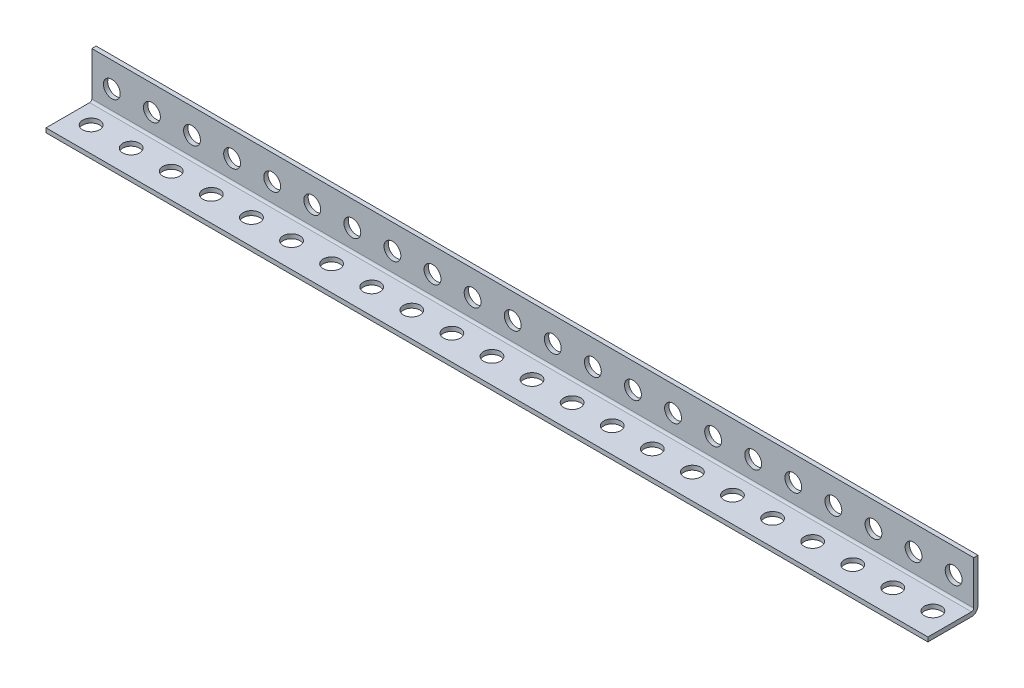
SolidWorks part; units mm, degrees
ref_plane "Front Plane" through (0, 0, 0) normal (0, 0, 1) x (1, 0, 0)
ref_plane "Top Plane" through (0, 0, 0) normal (0, 1, 0) x (1, 0, 0)
ref_plane "Right Plane" through (0, 0, 0) normal (1, 0, 0) x (0, 0, -1)
sketch "Sketch1" plane through (0, 0, 0) normal (1, 0, 0) x (0, 0, -1)
  line L0 (-15.875, -13.1318) -> (13.1318, -13.1318) construction
  line L1 (13.1318, -13.1318) -> (13.1318, 15.875) construction
  line L2 (13.1318, 15.875) -> (15.875, 15.875) construction
  line L3 (15.875, 15.875) -> (15.875, -15.875) construction
  line L4 (15.875, -15.875) -> (-15.875, -15.875) construction
  line L5 (-15.875, -15.875) -> (-15.875, -13.1318) construction
  line L6 (0, -15.875) -> (0, 15.875) construction
  line L7 (15.875, 0) -> (-15.875, 0) construction
  dimension "Thickness | T" = 2.7432
  dimension "Width (A)" = 31.75
  dimension "Width (B)" = 31.75
sketch "Sketch2" plane through (0, 0, 0) normal (0, 0, 1) x (1, 0, 0)
  line L0 (-609.6, 0) -> (609.6, 0) construction
  line L1 (-609.6, 15.875) -> (609.6, 15.875) construction
  line L2 (-609.6, 15.875) -> (-609.6, -15.875) construction
  line L3 (-609.6, -15.875) -> (609.6, -15.875) construction
  line L4 (609.6, 15.875) -> (609.6, -15.875) construction
  line L5 (0, 15.875) -> (0, -15.875) construction
  line L7 (-609.6, -13.1318) -> (609.6, -13.1318) construction
  circle A0 centre (596.9, 0) radius 5.334 construction
  circle A1 centre (571.5, 0) radius 5.334 construction
  point P15 (533.4, 0)
  point P16 (-533.4, 0)
  point P24 (602.234, 0)
  dimension "Mounting Hole Diameter" = 10.668
  dimension "Length | L" = 1219.2
  dimension "Mounting Hole Center to Center" = 25.4
  dimension "D1" = 12.7
  dimension "D2" = 63.5
sketch "Sketch3" plane through (0, 0, 0) normal (0, 1, 0) x (1, 0, 0)
  line L1 (-609.6, 15.875) -> (609.6, 15.875) construction
  line L2 (-609.6, 15.875) -> (-609.6, -15.875) construction
  line L3 (-609.6, -15.875) -> (609.6, -15.875) construction
  line L4 (609.6, 15.875) -> (609.6, -15.875) construction
  line L5 (-609.6, 13.1318) -> (609.6, 13.1318) construction
  line L7 (-609.6, 0) -> (609.6, 0) construction
  circle A0 centre (596.9, 0) radius 5.334 construction
  circle A1 centre (571.5, 0) radius 5.334 construction
  point P19 (-533.4, 0)
  point P21 (602.234, 0)
  point P22 (533.4, 0)
sketch "Sketch4" plane through (0, 0, 0) normal (1, 0, 0) x (0, 0, -1)
  line L0 (-15.875, -13.1318) -> (11.7602, -13.1318)
  line L1 (13.1318, -11.7602) -> (13.1318, 15.875)
  line L2 (13.1318, 15.875) -> (15.875, 15.875)
  line L3 (15.875, 15.875) -> (15.875, -11.7602)
  line L4 (11.7602, -15.875) -> (-15.875, -15.875)
  line L5 (-15.875, -15.875) -> (-15.875, -13.1318)
  line L6 (11.7602, -13.1318) -> (11.7602, -10.3886) construction
  arc A0 (11.7602, -13.1318) -> (13.1318, -11.7602) centre (11.7602, -11.7602) ccw
  arc A1 (15.875, -11.7602) -> (11.7602, -15.875) centre (11.7602, -11.7602) cw
extrude "Boss-Extrude1" add sketch "Sketch4" along normal up to vertex (609.6 mm away) and the other way up to vertex (609.6 mm away) up to point (609.6, 0, 0) other way up to point (-609.6, 0, 0)
sketch "Sketch5" plane through (0, 0, 0) normal (0, 0, 1) x (1, 0, 0)
  circle A0 centre (596.9, 0) radius 5.334
extrude "Cut-Extrude1" cut sketch "Sketch5" against normal through all
sketch "Sketch6" plane through (0, 0, 0) normal (0, 1, 0) x (1, 0, 0)
  circle A0 centre (596.9, 0) radius 5.334
extrude "Cut-Extrude2" cut sketch "Sketch6" against normal through all
pattern_linear "LPattern1" count 48 spacing 25.4 along (-1, 0, 0) of "Cut-Extrude2", "Cut-Extrude1"
sketch "Sketch7" plane through (0, 0, -15.875) normal (0, 0, -1) x (-1, 0, 0)
  line L0 (-609.6, -15.875) -> (609.6, -15.875) construction
  line L1 (-609.6, 15.875) -> (25.4, 15.875)
  line L2 (-609.6, 15.875) -> (-609.6, -15.875)
  line L3 (-609.6, -15.875) -> (25.4, -15.875)
  line L4 (25.4, 15.875) -> (25.4, -15.875)
  line L5 (602.234, 0) -> (609.6, 0) construction
  line L6 (609.6, -11.7602) -> (609.6, 15.875) construction
  line L7 (32.766, 0) -> (25.4, 0)
  circle A0 centre (596.9, 0) radius 5.334 construction
  circle A1 centre (38.1, 0) radius 5.334 construction
  dimension "D1" = 7.366
extrude "Cut-Extrude3" cut sketch "Sketch7" against normal blind 70 contours L4 L1 L2 L3 region at (292.1, 0, -15.875)
sketch "Sketch8" plane through (0, 0, -15.875) normal (0, 0, -1) x (-1, 0, 0)
  line L0 (25.4, -15.875) -> (609.6, -15.875) construction
  line L1 (25.4, 15.875) -> (50.8, 15.875)
  line L2 (25.4, 15.875) -> (25.4, -15.875)
  line L3 (25.4, -15.875) -> (50.8, -15.875)
  line L4 (50.8, 15.875) -> (50.8, -15.875)
  line L6 (58.166, 0) -> (50.8, 0)
  circle A0 centre (63.5, 0) radius 5.334 construction
  circle M28 centre (38.1, 0) radius 5.334
  line M29 (25.4, 15.875) -> (25.4, -11.7602)
  line M30 (25.4, -11.7602) -> (609.6, -11.7602)
  line M32 (609.6, 15.875) -> (25.4, 15.875)
  dimension "D1" = 7.366
extrude "Cut-Extrude4" cut sketch "Sketch8" against normal blind 70 contours L4 M32 M29 M30 M28 | L4 L2 L3 M30 region at (-38.1, 15.4997, -15.875) region at (-38.1, -13.8176, -15.875)
sketch "Sketch9" plane through (0, 0, -15.875) normal (0, 0, -1) x (-1, 0, 0)
  line L0 (602.234, 0) -> (609.6, 0)
  line L1 (609.6, -11.7602) -> (609.6, 15.875) construction
  line L2 (596.9, 5.334) -> (596.9, 15.875)
  line L3 (50.8, 15.875) -> (609.6, 15.875) construction
  line L4 (58.166, 0) -> (50.8, 0)
  line L5 (50.8, 15.875) -> (50.8, -11.7602) construction
  line L6 (63.5, 5.334) -> (63.5, 15.875)
  circle A0 centre (596.9, 0) radius 5.334 construction
  circle A1 centre (63.5, 0) radius 5.334 construction
sketch "Sketch10" plane through (0, -15.875, 0) normal (0, -1, 0) x (1, 0, 0)
  line L0 (-58.166, 0) -> (-50.8, 0)
  line L1 (-50.8, 15.875) -> (-50.8, -11.7602) construction
  line L2 (-63.5, 5.334) -> (-63.5, 15.875)
  line L3 (-50.8, 15.875) -> (-609.6, 15.875) construction
  line L4 (-602.234, 0) -> (-609.6, 0)
  line L5 (-609.6, 15.875) -> (-609.6, -11.7602) construction
  line L6 (-596.9, 5.334) -> (-596.9, 15.875)
  circle A0 centre (-63.5, 0) radius 5.334 construction
  circle A1 centre (-596.9, 0) radius 5.334 construction
equation "\"D1@Sketch2\"= ( \"Length | L@Sketch2\" - \"Mounting Hole Center to Center@Sketch2\" * \"Num Holes\" ) / 2"
equation "\"Num Holes\"= int ( \"Length | L@Sketch2\" / \"Mounting Hole Center to Center@Sketch2\" ) - 1"
equation "\"D2@Sketch2\"=\"Mounting Hole Center to Center@Sketch2\"*2.5"
equation "\"D3@LPattern1\"=\"Mounting Hole Center to Center@Sketch2\""
